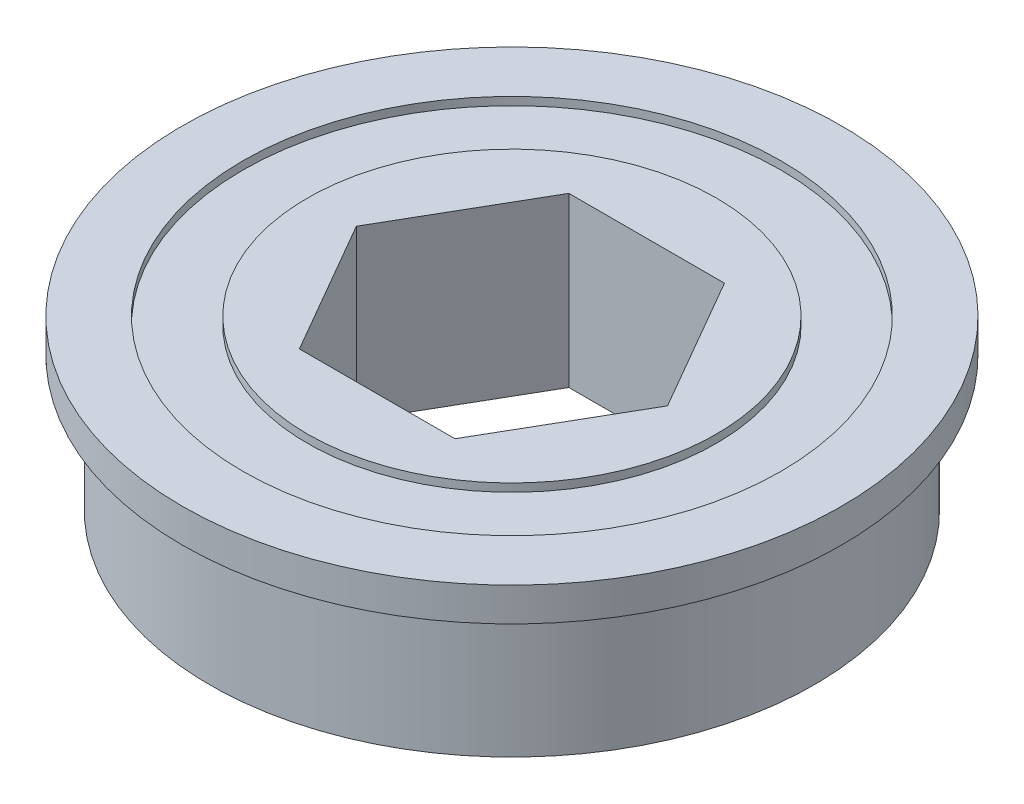
SolidWorks part; units mm, degrees
ref_plane "Front Plane" through (0, 0, 0) normal (0, 0, 1) x (1, 0, 0)
ref_plane "Top Plane" through (0, 0, 0) normal (0, 1, 0) x (1, 0, 0)
ref_plane "Right Plane" through (0, 0, 0) normal (1, 0, 0) x (0, 0, -1)
ref_plane "Plane1" through (0, 0, 0) normal (0, 0, -1) x (-1, 0, 0)
sketch "Sketch1" plane through (0, 0, 0) normal (0, 0, -1) x (-1, 0, 0)
  line L0 (-14.0583, 5.975) -> (0, 5.975)
  line L1 (0, 5.975) -> (0, 7.9375)
  line L2 (0, 7.9375) -> (-15.5575, 7.9375)
  line L3 (-15.5575, 7.9375) -> (-15.5575, 6.35)
  line L4 (-15.5575, 6.35) -> (-14.2748, 6.35)
  line L5 (0, 5.975) -> (0, 7.9375) construction
  arc A0 (-14.2748, 6.35) -> (-14.0583, 5.975) centre (-14.2748, 6.1) cw
revolve "Revolve1" add sketch "Sketch1" angle 360 about L5 reverse direction yes
sketch "Sketch2" plane through (0, 5.975, 0) normal (0, -1, 0) x (1, 0, 0)
  circle A0 centre (0, 0) radius 14.0583
extrude "Boss-Extrude1" add sketch "Sketch2" along normal blind 0.375 draft 30 draft outward yes
sketch "Sketch3" plane through (0, 5.6, 0) normal (0, -1, 0) x (1, 0, 0)
  circle A0 centre (0, 0) radius 14.2748
extrude "Boss-Extrude2" add sketch "Sketch3" along normal blind 5.6
sketch "Sketch4" plane through (0, 0, 0) normal (0, -1, 0) x (1, 0, 0)
  circle A0 centre (0, 0) radius 12.7
extrude "Cut-Extrude1" cut sketch "Sketch4" against normal blind 0.381
sketch "Sketch5" plane through (0, 0.381, 0) normal (0, -1, 0) x (1, 0, 0)
  circle A0 centre (0, 0) radius 9.652
extrude "Boss-Extrude3" add sketch "Sketch5" along normal blind 0.381
sketch "Sketch6" plane through (0, 7.9375, 0) normal (0, 1, 0) x (-1, 0, 0)
  circle A0 centre (0, 0) radius 12.7
extrude "Cut-Extrude2" cut sketch "Sketch6" against normal blind 0.381
sketch "Sketch7" plane through (0, 7.5565, 0) normal (0, 1, 0) x (-1, 0, 0)
  circle A0 centre (0, 0) radius 9.652
extrude "Boss-Extrude4" add sketch "Sketch7" along normal blind 0.381
sketch "Sketch8" plane through (0, 7.9375, 0) normal (0, 1, 0) x (-1, 0, 0)
  line L0 (7.3439, 0) -> (3.6719, 6.36)
  line L1 (3.6719, 6.36) -> (-3.6719, 6.36)
  line L2 (-3.6719, 6.36) -> (-7.3439, 0)
  line L3 (-7.3439, 0) -> (-3.6719, -6.36)
  line L4 (-3.6719, -6.36) -> (3.6719, -6.36)
  line L5 (3.6719, -6.36) -> (7.3439, 0)
extrude "Cut-Extrude3" cut sketch "Sketch8" against normal through all
ref_axis "Axis1" through (0, 0, 0) along (0, 1, 0)
